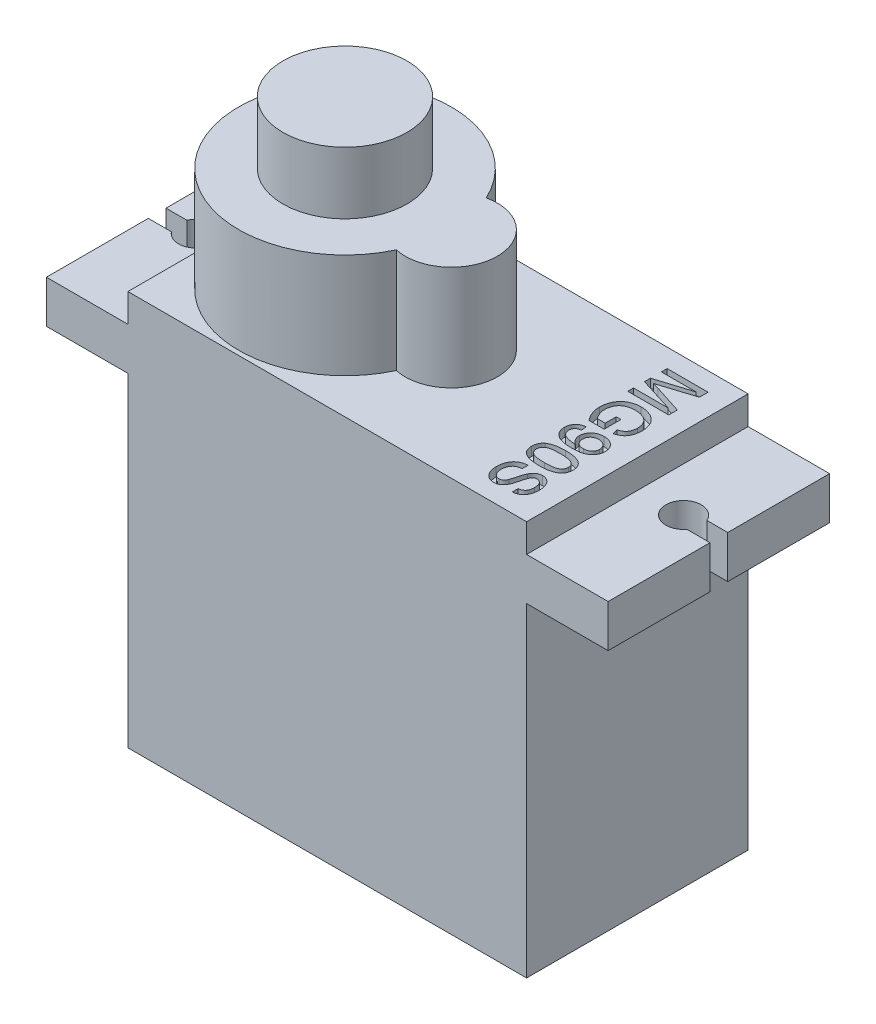
SolidWorks part; units mm, degrees
ref_plane "前视基准面" through (0, 0, 0) normal (0, 0, 1) x (1, 0, 0)
ref_plane "上视基准面" through (0, 0, 0) normal (0, 1, 0) x (1, 0, 0)
ref_plane "右视基准面" through (0, 0, 0) normal (1, 0, 0) x (0, 0, -1)
other "Configuration Table"
ref_axis "舵机转动基准轴" through (0, 0, 0) along (0, 1, 0)
ref_plane "基准面1" through (0, 20.7, 0) normal (0, 1, 0) x (1, 0, 0)
sketch "草图1" plane through (0, 0, 0) normal (0, 1, 0) x (1, 0, 0)
  line L1 (-6, 6.25) -> (16.5, 6.25)
  line L2 (-6, 6.25) -> (-6, -6.25)
  line L3 (-6, -6.25) -> (16.5, -6.25)
  line L4 (16.5, 6.25) -> (16.5, -6.25)
  point P4 (-6, 0)
  dimension "D1" = 22.5
  dimension "D2" = 12.5
  dimension "D3" = 6
extrude "凸台-拉伸1" add sketch "草图1" along normal blind 22.3
ref_plane "对称基准面" through (5.25, 0, 0) normal (1, 0, 0) x (0, 0, -1)
sketch "草图2" plane through (0, 22.3, 0) normal (0, 1, 0) x (1, 0, 0)
  line L0 (0, 0) -> (6, 0) construction
  circle A0 centre (0, 0) radius 6
  circle A1 centre (6, 0) radius 2.6
  dimension "D1" = 12
  dimension "D2" = 5.2
  dimension "D3" = 6
extrude "凸台-拉伸2" add sketch "草图2" along normal blind 5.9 contours A1 A0 | A0 A1 | A1 region at (6.9958, 22.3, 0) region at (-0.4473, 22.3, 0)
sketch "草图3" plane through (0, 28.2, 0) normal (0, 1, 0) x (1, 0, 0)
  circle A0 centre (0, 0) radius 3.5
  dimension "D1" = 7
extrude "凸台-拉伸3" add sketch "草图3" along normal blind 3.5 contours A0 region at (0, 28.2, 0)
sketch "草图4" plane through (0, 20.7, 0) normal (0, 1, 0) x (1, 0, 0)
  line L0 (16.5, 6.25) -> (16.5, -6.25)
  line L1 (16.5, -6.25) -> (21.1, -6.25)
  line L2 (21.1, -6.25) -> (21.1, -0.5)
  line L3 (21.1, -0.5) -> (19.7939, -0.5)
  line L4 (16.5, 6.25) -> (21.1, 6.25)
  line L5 (21.1, 6.25) -> (21.1, 0.5)
  line L6 (21.1, 0.5) -> (19.92, 0.5)
  line L7 (0, 0) -> (11.6357, 0) construction
  arc A0 (19.92, 0.5) -> (19.7939, -0.5) centre (19, 0.1081) ccw
  dimension "D4" = 1
  dimension "D1" = 4.6
  dimension "D2" = 1
  dimension "D5" = 2.1
extrude "凸台-拉伸4" add sketch "草图4" against normal blind 2.4
mirror "镜向1" about plane through (5.25, 0, 0) normal (1, 0, 0) of "凸台-拉伸4"
sketch "草图5" plane through (-6, 0, 0) normal (-1, 0, 0) x (0, 0, 1)
  line L0 (-0.95, 4.7) -> (0.95, 4.7) construction
  line L1 (-0.95, 5.3) -> (0.95, 5.3)
  line L2 (-0.95, 4.1) -> (0.95, 4.1)
  line L3 (0, 0) -> (0, 69.0457) construction
  line L4 (-6.25, 0) -> (6.25, 0) construction
  arc A0 (-0.95, 5.3) -> (-0.95, 4.1) centre (-0.95, 4.7) ccw
  arc A1 (0.95, 4.1) -> (0.95, 5.3) centre (0.95, 4.7) ccw
  point P2 (0, 4.7)
  dimension "D3" = 0.6
  dimension "D1" = 1.9
  dimension "D2" = 4.7
extrude "凸台-拉伸5" add sketch "草图5" along normal blind 3
sketch "草图6" plane through (0, 22.3, 0) normal (0, 1, 0) x (1, 0, 0)
  line L0 (12.9807, 6.25) -> (12.9807, -6.25) construction
  line L1 (16.5, 6.25) -> (-6, 6.25) construction
  line L2 (-6, -6.25) -> (16.5, -6.25) construction
  text T0 "MG90S" font "Arial" height in points 9
extrude "切除-拉伸1" cut sketch "草图6" against normal blind 0.5
